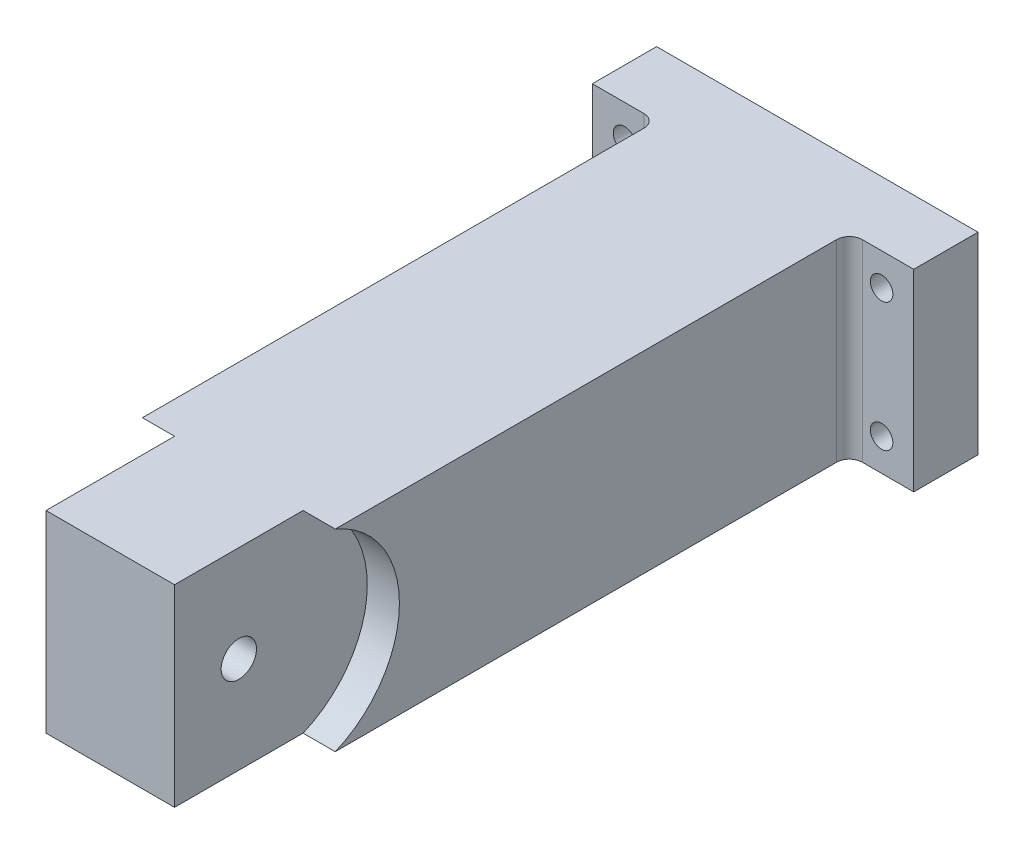
SolidWorks part; units mm, degrees
ref_plane "Plan de face" through (0, 0, 0) normal (0, 0, 1) x (1, 0, 0)
ref_plane "Plan de dessus" through (0, 0, 0) normal (0, 1, 0) x (1, 0, 0)
ref_plane "Plan de droite" through (0, 0, 0) normal (1, 0, 0) x (0, 0, -1)
sketch "Esquisse1" plane through (0, 0, 0) normal (0, 0, 1) x (1, 0, 0)
  line L1 (0, 0) -> (50, 0)
  line L2 (0, 0) -> (0, 30)
  line L3 (0, 30) -> (50, 30)
  line L4 (50, 0) -> (50, 30)
  dimension "D1" = 50
  dimension "D2" = 30
extrude "Boss.-Extru.1" add sketch "Esquisse1" along normal blind 10
sketch "Esquisse2" plane through (0, 0, 10) normal (0, 0, 1) x (1, 0, 0)
  line L0 (50, 30) -> (0, 30) construction
  line L1 (10, 30) -> (40, 30)
  line L2 (10, 30) -> (10, 0)
  line L3 (10, 0) -> (40, 0)
  line L4 (40, 30) -> (40, 0)
  line L5 (0, 0) -> (50, 0) construction
  line L6 (10, 30) -> (0, 30) construction
  line L7 (40, 30) -> (50, 30) construction
  dimension "D1" = 30
extrude "Boss.-Extru.2" add sketch "Esquisse2" along normal blind 100
sketch "Esquisse3" plane through (0, 0, 10) normal (0, 0, 1) x (1, 0, 0)
  line L0 (45, 30) -> (45, 25) construction
  line L3 (5, 30) -> (5, 25) construction
  line L6 (50, 30) -> (40, 30) construction
  line L7 (45, 25) -> (45, 5) construction
  line L8 (45, 5) -> (45, 0) construction
  line L9 (40, 0) -> (50, 0) construction
  line L10 (10, 30) -> (0, 30) construction
  line L11 (5, 25) -> (5, 5) construction
  line L12 (5, 5) -> (5, 0) construction
  line L13 (0, 0) -> (10, 0) construction
  circle A0 centre (45, 25) radius 1.75
  circle A1 centre (45, 5) radius 1.75
  circle A2 centre (5, 25) radius 1.75
  circle A3 centre (5, 5) radius 1.75
  dimension "D2" = 3.5
  dimension "D1" = 5
extrude "Enlèv. mat.-Extru.1" cut sketch "Esquisse3" against normal through all
fillet "Congé1" radius 2 2 edges at (10, 15, 10) (40, 15, 10)
sketch "Esquisse5" plane through (10, 0, 0) normal (-1, 0, 0) x (0, 0, 1)
  line L0 (110, 0) -> (12, 0) construction
  line L1 (110, 30) -> (90, 30)
  line L2 (110, 30) -> (110, 0)
  line L3 (110, 0) -> (90, 0)
  line L4 (90, 30) -> (90, 0) construction
  arc A0 (90, 30) -> (90, 0) centre (96.2803, 15) ccw
  dimension "D1" = 20
extrude "Enlèv. mat.-Extru.3" cut sketch "Esquisse5" against normal blind 5
ref_plane "Plan1" through (25, 0, 0) normal (-1, 0, 0) x (0, 0, 1)
mirror "Symétrie1" about plane through (25, 0, 0) normal (-1, 0, 0) of "Enlèv. mat.-Extru.3"
sketch "Esquisse6" plane through (15, 0, 0) normal (-1, 0, 0) x (0, 0, 1)
  line L0 (90, 0) -> (110, 30) construction
  circle A0 centre (100, 15) radius 2.75
  dimension "D1" = 5.5
extrude "Enlèv. mat.-Extru.4" cut sketch "Esquisse6" against normal through all
